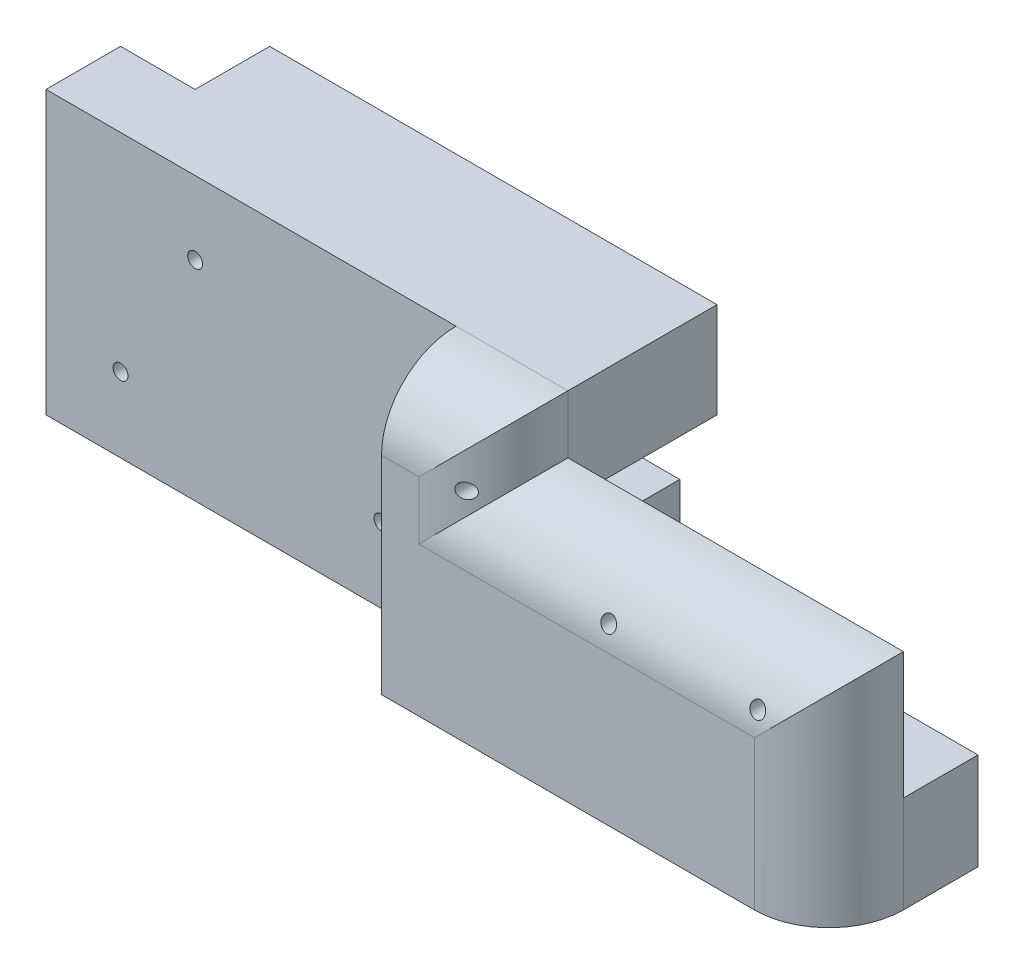
SolidWorks part; units mm, degrees
ref_plane "Plan de face" through (0, 0, 0) normal (0, 0, 1) x (1, 0, 0)
ref_plane "Plan de dessus" through (0, 0, 0) normal (0, 1, 0) x (1, 0, 0)
ref_plane "Plan de droite" through (0, 0, 0) normal (1, 0, 0) x (0, 0, -1)
sketch "Esquisse1" plane through (0, 0, 40) normal (0, 0, 1) x (1, 0, 0)
  line L0 (-121.1414, 49.5358) -> (-121.1414, 19.5358)
  line L1 (-121.1414, 49.5358) -> (-181.1414, 49.5358)
  line L2 (-121.1414, 19.5358) -> (-181.1414, 19.5358)
  line L3 (-181.1414, 49.5358) -> (-181.1414, 19.5358)
  dimension "D1" = 30
  dimension "D2" = 60
extrude "Boss.-Extru.1" add sketch "Esquisse1" along normal blind 10
sketch "Esquisse2" plane through (0, 0, 40) normal (0, 0, -1) x (-1, 0, 0)
  line L0 (166.1414, 44.5358) -> (181.1414, 44.5358)
  line L1 (166.1414, 44.5358) -> (166.1414, 57.3381)
  line L2 (181.1414, 44.5358) -> (181.1414, 57.3381)
  line L3 (166.1414, 57.3381) -> (181.1414, 57.3381)
  line L4 (181.1414, 49.5358) -> (181.1414, 19.5358) construction
extrude "Boss.-Extru.2" add sketch "Esquisse2" along normal blind 20 and the other way blind 10
sketch "Esquisse3" plane through (0, 0, 40) normal (0, 0, -1) x (-1, 0, 0)
  line L0 (161.1414, 44.5358) -> (181.1414, 44.5358)
  line L1 (161.1414, 44.5358) -> (161.1414, 19.5358)
  line L2 (181.1414, 44.5358) -> (181.1414, 19.5358)
  line L3 (161.1414, 19.5358) -> (181.1414, 19.5358)
  line L4 (121.1414, 19.5358) -> (121.1414, 32.5358)
  line L5 (121.1414, 19.5358) -> (161.1414, 19.5358)
  line L6 (121.1414, 32.5358) -> (161.1414, 32.5358)
  line L7 (161.1414, 19.5358) -> (161.1414, 32.5358)
  line L10 (121.1414, 19.5358) -> (121.1414, 49.5358) construction
  line L11 (161.1414, 32.5358) -> (121.1414, 32.5358) construction
  line L12 (181.1414, 19.5358) -> (121.1414, 19.5358) construction
  line L13 (181.1414, 44.5358) -> (181.1414, 19.5358) construction
  line M3 (181.1414, 44.5358) -> (166.1414, 44.5358)
  line M6 (121.1414, 49.5358) -> (121.1414, 19.5358)
  line M7 (121.1414, 19.5358) -> (181.1414, 19.5358)
  line M8 (181.1414, 19.5358) -> (181.1414, 44.5358)
extrude "Boss.-Extru.3" add sketch "Esquisse3" along normal blind 10 contours L6 L1 M6 M7 | L0 L1 M7 M8 M3 region at (-171.1414, 32.0358, 40) region at (-141.1414, 26.0358, 40)
sketch "Esquisse4" plane through (0, 0, 30) normal (0, 0, -1) x (-1, 0, 0)
  line L0 (181.1414, 19.5358) -> (181.1414, 57.3381)
  line L1 (181.1414, 19.5358) -> (236.1414, 19.5358)
  line L2 (181.1414, 57.3381) -> (236.1414, 57.3381)
  line L3 (236.1414, 19.5358) -> (236.1414, 57.3381)
  line L5 (236.1414, 59.5358) -> (236.1414, 9.5358) construction
  line L6 (181.1414, 57.3381) -> (166.1414, 57.3381) construction
extrude "Boss.-Extru.4" add sketch "Esquisse4" against normal blind 10
sketch "Esquisse5" plane through (0, 0, 30) normal (0, 0, -1) x (-1, 0, 0)
  line L0 (181.1414, 44.5358) -> (181.1414, 57.3381)
  line L1 (181.1414, 44.5358) -> (226.1414, 44.5358)
  line L2 (181.1414, 57.3381) -> (226.1414, 57.3381)
  line L3 (226.1414, 44.5358) -> (226.1414, 57.3381)
  line L4 (226.1414, 59.5358) -> (226.1414, 44.5358) construction
extrude "Boss.-Extru.5" add sketch "Esquisse5" along normal blind 10
sketch "Esquisse6" plane through (0, 0, 50) normal (0, 0, 1) x (1, 0, 0)
  line L0 (-181.1414, 19.5358) -> (-236.1414, 19.5358) construction
  line L1 (-236.1414, 19.5358) -> (-236.1414, 57.3381) construction
  line L2 (-181.1414, 57.3381) -> (-181.1414, 19.5358) construction
  circle A0 centre (-131.1414, 42.5358) radius 1
  circle A1 centre (-151.1414, 42.5358) radius 1
  circle A3 centre (-171.1414, 47.5358) radius 1
  circle A4 centre (-216.1414, 47.5358) radius 1
  circle A5 centre (-226.1414, 29.5358) radius 1
  circle A6 centre (-191.1414, 29.5358) radius 1
  circle A7 centre (-131.1414, 42.5358) radius 1 construction
  circle A8 centre (-151.1414, 42.5358) radius 1 construction
  circle A9 centre (-171.1414, 47.5358) radius 1 construction
  circle A10 centre (-216.1414, 47.5358) radius 1 construction
  dimension "D1" = 10
  dimension "D2" = 10
  dimension "D3" = 10
  dimension "D4" = 10
  dimension "D5" = 2
  dimension "D6" = 2
extrude "Enlèv. mat.-Extru.1" cut sketch "Esquisse6" against normal through all
fillet "Congé1" radius 10 4 edges at (-121.1414, 34.5358, 50) (-166.1414, 53.437, 50) (-173.6414, 57.3381, 50) (-143.6414, 49.5358, 50)
